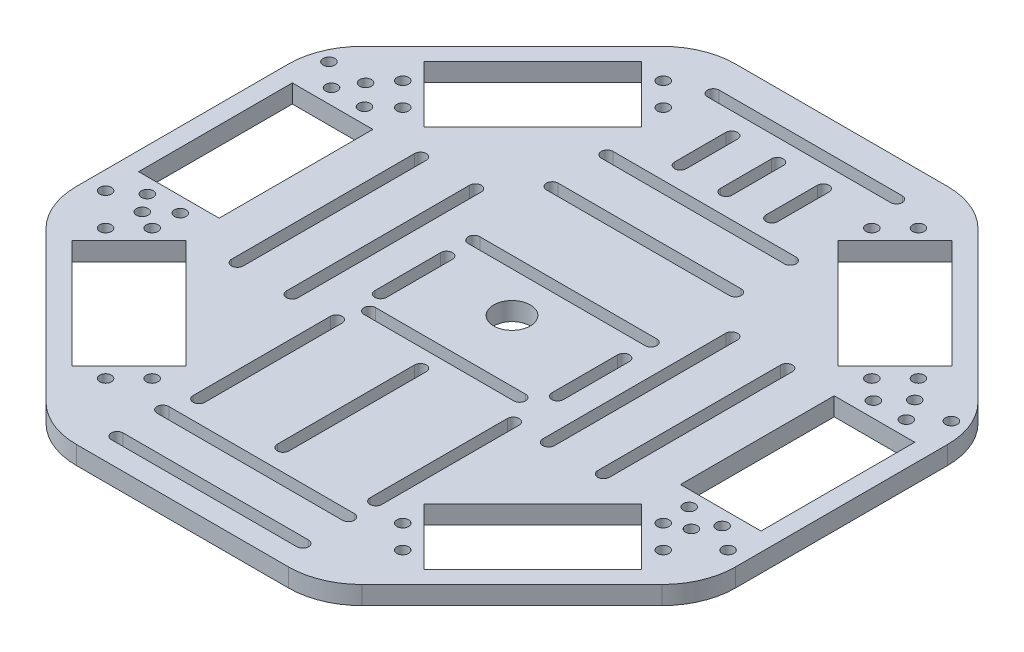
SolidWorks part; units mm, degrees
ref_plane "Front Plane" through (0, 0, 0) normal (0, 0, 1) x (1, 0, 0)
ref_plane "Top Plane" through (0, 0, 0) normal (0, 1, 0) x (1, 0, 0)
ref_plane "Right Plane" through (0, 0, 0) normal (1, 0, 0) x (0, 0, -1)
sketch "Sketch1" plane through (0, 0, 0) normal (0, 1, 0) x (1, 0, 0)
  line L1 (-90, -37.2792) -> (-37.2792, -90)
  line L2 (-37.2792, -90) -> (37.2792, -90)
  line L3 (37.2792, -90) -> (90, -37.2792)
  line L4 (90, -37.2792) -> (90, 37.2792)
  line L5 (90, 37.2792) -> (37.2792, 90)
  line L6 (37.2792, 90) -> (-37.2792, 90)
  line L7 (-37.2792, 90) -> (-90, 37.2792)
  line L8 (-90, 37.2792) -> (-90, -37.2792)
  line L12 (63.6396, -63.6396) -> (0, 0) construction
  line L21 (-20.4, -34.5422) -> (-34.5422, -20.4)
  line L22 (-20.4, -34.5422) -> (-50.0985, -64.2407)
  line L23 (-50.0985, -64.2407) -> (-64.2407, -50.0985)
  line L24 (-34.5422, -20.4) -> (-64.2407, -50.0985)
  line L25 (-38.85, -10) -> (-38.85, 10)
  line L26 (-38.85, -10) -> (-80.85, -10)
  line L27 (-80.85, -10) -> (-80.85, 10)
  line L28 (-38.85, 10) -> (-80.85, 10)
  line L29 (-34.5422, 20.4) -> (-20.4, 34.5422)
  line L30 (-34.5422, 20.4) -> (-64.2407, 50.0985)
  line L31 (-64.2407, 50.0985) -> (-50.0985, 64.2407)
  line L32 (-20.4, 34.5422) -> (-50.0985, 64.2407)
  line L37 (20.4, 34.5422) -> (34.5422, 20.4)
  line L38 (20.4, 34.5422) -> (50.0985, 64.2407)
  line L39 (50.0985, 64.2407) -> (64.2407, 50.0985)
  line L40 (34.5422, 20.4) -> (64.2407, 50.0985)
  line L41 (38.85, 10) -> (38.85, -10)
  line L42 (38.85, 10) -> (80.85, 10)
  line L43 (80.85, 10) -> (80.85, -10)
  line L44 (38.85, -10) -> (80.85, -10)
  circle A0 centre (0, 0) radius 90 construction
  circle A13 centre (0, 0) radius 90 construction
  circle A14 centre (-27.7186, -21.3546) radius 2.5
  circle A15 centre (-21.3546, -27.7186) radius 2.5
  circle A16 centre (-56.9221, -63.2861) radius 2.5
  circle A17 centre (-63.2861, -56.9221) radius 2.5
  circle A18 centre (0, 0) radius 90 construction
  circle A19 centre (-34.7, 4.5) radius 2.5
  circle A20 centre (-34.7, -4.5) radius 2.5
  circle A21 centre (-85, -4.5) radius 2.5
  circle A22 centre (-85, 4.5) radius 2.5
  circle A23 centre (0, 0) radius 90 construction
  circle A24 centre (-21.3546, 27.7186) radius 2.5
  circle A25 centre (-27.7186, 21.3546) radius 2.5
  circle A26 centre (-63.2861, 56.9221) radius 2.5
  circle A27 centre (-56.9221, 63.2861) radius 2.5
  circle A28 centre (0, 0) radius 90 construction
  circle A33 centre (0, 0) radius 90 construction
  circle A34 centre (27.7186, 21.3546) radius 2.5
  circle A35 centre (21.3546, 27.7186) radius 2.5
  circle A36 centre (56.9221, 63.2861) radius 2.5
  circle A37 centre (63.2861, 56.9221) radius 2.5
  circle A38 centre (0, 0) radius 90 construction
  circle A39 centre (34.7, -4.5) radius 2.5
  circle A40 centre (34.7, 4.5) radius 2.5
  circle A41 centre (85, 4.5) radius 2.5
  circle A42 centre (85, -4.5) radius 2.5
  circle A43 centre (0, 0) radius 90 construction
  point P15 (63.6396, -63.6396)
  point P16 (60.1041, -60.1041)
  point P17 (57.1696, -57.1696)
  point P121 (0, 0)
  dimension "D1" = 90
  dimension "D12" = 8
extrude "Baseplate" add sketch "Sketch1" along normal blind 5 contours L7 L8 L1 L2 L3 L4 L5 L6 A42 A41 A40 A39 A37 A36 A35 A34 A27 A26 A25 A24 A22 A21 A20 A19 A17 A16 A15 A14 L44 L41 | L29 L32 L31 L30 | L37 L40 L39 L38 | L41 L44 L43 L42 | L25 L28 L27 L26 | A27 | A26 | A25 | A24 | A22 | A21 | A19 | A20 | A14 | A15 | A17 | A16 | A40 | A41 | A42 | A35 | A34 | A39 | A37 | A36 | L21 L24 L23 L22 region at (1.7472, 0, 1.7472) region at (-59.85, 0, 0) region at (-42.3203, 0, -42.3203) region at (42.3203, 0, -42.3203) region at (59.85, 0, 0) region at (-27.7186, 0, 21.3546) region at (-21.3546, 0, 27.7186) region at (-56.9221, 0, 63.2861) region at (-63.2861, 0, 56.9221) region at (-34.7, 0, -4.5) region at (-34.7, 0, 4.5) region at (-85, 0, 4.5) region at (-85, 0, -4.5) region at (-21.3546, 0, -27.7186) region at (-27.7186, 0, -21.3546) region at (-63.2861, 0, -56.9221) region at (-56.9221, 0, -63.2861) region at (34.7, 0, -4.5) region at (85, 0, -4.5) region at (85, 0, 4.5)
fillet "Fillet1" radius 20 8 edges at (-90, 2.5, -37.2792) (-37.2792, 2.5, -90) (37.2792, 2.5, -90) (90, 2.5, -37.2792) (90, 2.5, 37.2792) (37.2792, 2.5, 90) (-37.2792, 2.5, 90) (-90, 2.5, 37.2792)
sketch "Sketch2" plane through (0, 5, 0) normal (0, 1, 0) x (1, 0, 0)
  line L0 (90, -28.9949) -> (90, 28.9949) construction
  line L1 (63, 25.0051) -> (85, 25.0051)
  line L2 (63, 25.0051) -> (63, -16.9949)
  line L3 (63, -16.9949) -> (85, -16.9949)
  line L4 (85, 25.0051) -> (85, -16.9949)
  circle A0 centre (78.5, 29.2051) radius 1.6
  circle A1 centre (69.5, 29.2051) radius 1.6
  circle A2 centre (69.5, -21.0949) radius 1.6
  circle A3 centre (78.5, -21.0949) radius 1.6
  point P8 (74, 25.0051)
  dimension "D1" = 3.2
  dimension "D2" = 9
  dimension "D3" = 50.3
  dimension "D4" = 22
  dimension "D5" = 42
  dimension "D6" = 4.2
  dimension "D7" = 4.5
  dimension "D8" = 5
  dimension "D9" = 12
extrude "Servo hole" cut sketch "Sketch2" against normal through all contours A0 | L4 L1 L2 L3 | A2 | A3 | A1 region at (74, 5, -4.0051) region at (78.5, 5, -29.2051) region at (69.5, 5, 21.0949) region at (78.5, 5, 21.0949)
sketch "Sketch3" plane through (0, 5, 0) normal (0, 1, 0) x (1, 0, 0)
  circle A0 centre (0, 0) radius 5
  dimension "D1" = 10
extrude "Center hole" cut sketch "Sketch3" against normal through all
pattern_circular "Servo hole pattern" count 8 over 360 about axis through (0, 5, 0) along (0, 1, 0) skipping 2, 3, 4, 5, 6 of "Servo hole"
sketch "Sketch4" plane through (0, 5, 0) normal (0, 1, 0) x (1, 0, 0)
  line L0 (-28.9949, -90) -> (28.9949, -90) construction
  line L1 (-90, 28.9949) -> (-90, -28.9949) construction
  circle A0 centre (-23, 5.1332) radius 1.6
  circle A1 centre (-23, -70) radius 1.6
  circle A2 centre (25.3362, 12.6262) radius 1.6
  circle A3 centre (25.3362, -70) radius 1.6
  circle A4 centre (-7.5585, -18.3745) radius 1.6
  circle A5 centre (20.4577, -18.3745) radius 1.6
  dimension "D1" = 3.2
  dimension "D8" = 20
  dimension "D2" = 7.493
  dimension "D3" = 48.3362
  dimension "D4" = 31.0007
  dimension "D5" = 51.6255
  dimension "D6" = 4.8785
  dimension "D7" = 28.0162
  dimension "D9" = 67
extrude "Arduino Screw holes" cut sketch "Sketch4" against normal through all
ref_plane "Midplane" through (0, 0, 0) normal (1, 0, 0) x (0, 0, -1)
mirror "Mirror1" about plane through (0, 0, 0) normal (1, 0, 0) of "Servo hole pattern", "Servo hole"
sketch "Sketch5" plane through (0, 5, 0) normal (0, 1, 0) x (1, 0, 0)
  line L0 (-25, 36) -> (25, 36) construction
  line L1 (-25, 37.6) -> (25, 37.6)
  line L2 (-25, 34.4) -> (25, 34.4)
  line L3 (-25, 51) -> (25, 51) construction
  line L4 (-25, 52.6) -> (25, 52.6)
  line L5 (-25, 49.4) -> (25, 49.4)
  line L6 (-50, 25) -> (-50, -25) construction
  line L7 (-48.4, 25) -> (-48.4, -25)
  line L8 (-51.6, 25) -> (-51.6, -25)
  line L9 (-35, 25) -> (-35, -25) construction
  line L10 (-33.4, 25) -> (-33.4, -25)
  line L11 (-36.6, 25) -> (-36.6, -25)
  line L12 (35, 25) -> (35, -25) construction
  line L13 (36.6, 25) -> (36.6, -25)
  line L14 (33.4, 25) -> (33.4, -25)
  line L15 (50, 25) -> (50, -25) construction
  line L16 (51.6, 25) -> (51.6, -25)
  line L17 (48.4, 25) -> (48.4, -25)
  line L18 (-25, 80) -> (25, 80) construction
  line L19 (-25, 81.6) -> (25, 81.6)
  line L20 (-25, 78.4) -> (25, 78.4)
  line L21 (-12.5, 72.5) -> (-12.5, 58.5) construction
  line L22 (-10.9, 72.5) -> (-10.9, 58.5)
  line L23 (-14.1, 72.5) -> (-14.1, 58.5)
  line L24 (12.5, 72.5) -> (12.5, 58.5) construction
  line L25 (14.1, 72.5) -> (14.1, 58.5)
  line L26 (10.9, 72.5) -> (10.9, 58.5)
  line L27 (28.9949, 90) -> (-28.9949, 90) construction
  line L28 (0, 72.5) -> (0, 58.5) construction
  line L29 (1.6, 72.5) -> (1.6, 58.5)
  line L30 (-1.6, 72.5) -> (-1.6, 58.5)
  arc A0 (-25, 37.6) -> (-25, 34.4) centre (-25, 36) ccw
  arc A1 (25, 34.4) -> (25, 37.6) centre (25, 36) ccw
  arc A2 (-25, 52.6) -> (-25, 49.4) centre (-25, 51) ccw
  arc A3 (25, 49.4) -> (25, 52.6) centre (25, 51) ccw
  arc A4 (-48.4, 25) -> (-51.6, 25) centre (-50, 25) ccw
  arc A5 (-51.6, -25) -> (-48.4, -25) centre (-50, -25) ccw
  arc A6 (-33.4, 25) -> (-36.6, 25) centre (-35, 25) ccw
  arc A7 (-36.6, -25) -> (-33.4, -25) centre (-35, -25) ccw
  arc A8 (36.6, 25) -> (33.4, 25) centre (35, 25) ccw
  arc A9 (33.4, -25) -> (36.6, -25) centre (35, -25) ccw
  arc A10 (51.6, 25) -> (48.4, 25) centre (50, 25) ccw
  arc A11 (48.4, -25) -> (51.6, -25) centre (50, -25) ccw
  arc A12 (-25, 81.6) -> (-25, 78.4) centre (-25, 80) ccw
  arc A13 (25, 78.4) -> (25, 81.6) centre (25, 80) ccw
  arc A14 (-10.9, 72.5) -> (-14.1, 72.5) centre (-12.5, 72.5) ccw
  arc A15 (-14.1, 58.5) -> (-10.9, 58.5) centre (-12.5, 58.5) ccw
  arc A16 (14.1, 72.5) -> (10.9, 72.5) centre (12.5, 72.5) ccw
  arc A17 (10.9, 58.5) -> (14.1, 58.5) centre (12.5, 58.5) ccw
  arc A18 (1.6, 72.5) -> (-1.6, 72.5) centre (0, 72.5) ccw
  arc A19 (-1.6, 58.5) -> (1.6, 58.5) centre (0, 58.5) ccw
  point P2 (0, 36)
  point P7 (0, 51)
  point P14 (-50, 0)
  point P21 (-35, 0)
  point P28 (35, 0)
  point P35 (50, 0)
  point P42 (0, 80)
  point P48 (-12.5, 65.5)
  point P57 (12.5, 65.5)
  point P64 (0, 65.5)
  dimension "D1" = 1.6
  dimension "D7" = 50
  dimension "D2" = 15
  dimension "D3" = 15
  dimension "D4" = 15
  dimension "D5" = 10
  dimension "D6" = 50
  dimension "D8" = 35
  dimension "D9" = 35
  dimension "D10" = 36
  dimension "D11" = 12.5
  dimension "D12" = 12.5
  dimension "D13" = 7.5
  dimension "D14" = 7.5
extrude "Slits" cut sketch "Sketch5" against normal through all contours L30 A19 L29 A18 | L26 A17 L25 A16 | L5 A3 L4 A2 | L2 A1 L1 A0 | L8 A5 L7 A4 | L11 A7 L10 A6 | L14 A9 L13 A8 | L17 A11 L16 A10 | L19 A13 L20 A12 | L22 A15 L23 A14 region at (0, 5, -36) region at (0, 5, -51) region at (-50, 5, 0) region at (-35, 5, 0) region at (35, 5, 0) region at (50, 5, 0) region at (12.5, 5, -65.5) region at (0, 5, -65.5)
sketch "Sketch6" plane through (0, 5, 0) normal (0, 1, 0) x (1, 0, 0)
  circle A0 centre (-75, 35) radius 1.6
  circle A1 centre (-85, 35) radius 1.6
  point P4 (0, 0)
  dimension "D1" = 3.2
  dimension "D3" = 10
  dimension "D4" = 85
  dimension "D5" = 35
extrude "Exterior Screw Holes" cut sketch "Sketch6" against normal through all
ref_plane "Plane1" through (0, 0, 0) normal (0, 0, 1) x (1, 0, 0)
mirror "Mirror2" about plane through (0, 0, 0) normal (1, 0, 0) of "Exterior Screw Holes"
sketch "Sketch7" plane through (0, 5, 0) normal (0, 1, 0) x (1, 0, 0)
  line L0 (-85, 35) -> (-85, 2.3324)
  circle A0 centre (-85, -26) radius 1.6
  circle A1 centre (-75, -26) radius 1.6
  point P4 (-86.5, -19.8866)
  point P5 (0, 0)
  dimension "D1" = 3.2
  dimension "D3" = 10
  dimension "D4" = 61
extrude "Cut-Extrude1" cut sketch "Sketch7" against normal through all contours A1 | A0 region at (-75, 5, 26)
mirror "Mirror3" about plane through (0, 0, 0) normal (1, 0, 0) of "Cut-Extrude1"
sketch "Sketch8" plane through (0, 5, 0) normal (0, 1, 0) x (1, 0, 0)
  line L0 (20.4577, -18.3745) -> (-20.4577, -18.3745) construction
  line L1 (20.4577, -19.9745) -> (-20.4577, -19.9745)
  line L2 (20.4577, -16.7745) -> (-20.4577, -16.7745)
  line L3 (0, -25.4762) -> (0, 25.4762) construction
  line L4 (25.3362, 12.6262) -> (-23, 12.6262) construction
  line L5 (25.3362, 11.0262) -> (-23, 11.0262)
  line L6 (25.3362, 14.2262) -> (-23, 14.2262)
  line L7 (-23, -12.8668) -> (-23, 5.1332) construction
  line L8 (-24.6, -12.8668) -> (-24.6, 5.1332)
  line L9 (-21.4, -12.8668) -> (-21.4, 5.1332)
  line L10 (25.3362, 5.1332) -> (25.3362, -12.8668) construction
  line L11 (26.9362, 5.1332) -> (26.9362, -12.8668)
  line L12 (23.7362, 5.1332) -> (23.7362, -12.8668)
  line L13 (-25.3362, -70) -> (25.3362, -70) construction
  line L14 (-25.3362, -68.4) -> (25.3362, -68.4)
  line L15 (-25.3362, -71.6) -> (25.3362, -71.6)
  line L16 (-23, -25) -> (-23, -62.5) construction
  line L17 (-21.4, -25) -> (-21.4, -62.5)
  line L18 (-24.6, -25) -> (-24.6, -62.5)
  line L19 (25.3362, -62.5) -> (25.3362, -25) construction
  line L20 (23.7362, -62.5) -> (23.7362, -25)
  line L21 (26.9362, -62.5) -> (26.9362, -25)
  line L22 (0, -62.5) -> (0, -25) construction
  line L23 (-1.6, -62.5) -> (-1.6, -25)
  line L24 (1.6, -62.5) -> (1.6, -25)
  line L25 (-25.3362, -82.5) -> (25.3362, -82.5) construction
  line L26 (-25.3362, -80.9) -> (25.3362, -80.9)
  line L27 (-25.3362, -84.1) -> (25.3362, -84.1)
  arc A0 (20.4577, -19.9745) -> (20.4577, -16.7745) centre (20.4577, -18.3745) ccw
  arc A1 (-20.4577, -16.7745) -> (-20.4577, -19.9745) centre (-20.4577, -18.3745) ccw
  circle A2 centre (-7.5585, -18.3745) radius 1.6 construction
  arc A3 (25.3362, 11.0262) -> (25.3362, 14.2262) centre (25.3362, 12.6262) ccw
  arc A4 (-23, 14.2262) -> (-23, 11.0262) centre (-23, 12.6262) ccw
  arc A5 (-24.6, -12.8668) -> (-21.4, -12.8668) centre (-23, -12.8668) ccw
  arc A6 (-21.4, 5.1332) -> (-24.6, 5.1332) centre (-23, 5.1332) ccw
  arc A7 (26.9362, 5.1332) -> (23.7362, 5.1332) centre (25.3362, 5.1332) ccw
  arc A8 (23.7362, -12.8668) -> (26.9362, -12.8668) centre (25.3362, -12.8668) ccw
  arc A9 (-25.3362, -68.4) -> (-25.3362, -71.6) centre (-25.3362, -70) ccw
  arc A10 (25.3362, -71.6) -> (25.3362, -68.4) centre (25.3362, -70) ccw
  arc A11 (-21.4, -25) -> (-24.6, -25) centre (-23, -25) ccw
  arc A12 (-24.6, -62.5) -> (-21.4, -62.5) centre (-23, -62.5) ccw
  arc A13 (23.7362, -62.5) -> (26.9362, -62.5) centre (25.3362, -62.5) ccw
  arc A14 (26.9362, -25) -> (23.7362, -25) centre (25.3362, -25) ccw
  arc A15 (-1.6, -62.5) -> (1.6, -62.5) centre (0, -62.5) ccw
  arc A16 (1.6, -25) -> (-1.6, -25) centre (0, -25) ccw
  arc A17 (-25.3362, -80.9) -> (-25.3362, -84.1) centre (-25.3362, -82.5) ccw
  arc A18 (25.3362, -84.1) -> (25.3362, -80.9) centre (25.3362, -82.5) ccw
  point P3 (0, -18.3745)
  point P8 (1.1681, 12.6262)
  point P20 (-23, -3.8668)
  point P30 (25.3362, -3.8668)
  point P35 (0, -70)
  point P40 (-23, -43.75)
  point P50 (25.3362, -43.75)
  point P57 (0, -43.75)
  point P65 (0, -82.5)
  dimension "D2" = 1.6
  dimension "D1" = 18
  dimension "D3" = 37.5
  dimension "D4" = 7.5
  dimension "D5" = 12.5
extrude "Cut-Extrude2" cut sketch "Sketch8" against normal through all contours L9 A6 L8 A5 | L12 A8 L11 A7 | L2 A1 L1 A0 | L24 A16 L23 A15 | L21 A14 L20 A13 | L27 A18 L26 A17 | L6 A4 L5 A3 | L17 A12 L18 A11 | L14 A10 L15 A9 region at (0, 5, 18.3745) region at (-23, 5, 3.8668) region at (25.3362, 5, 3.8668) region at (25.3362, 5, 43.75) region at (0, 5, 43.75) region at (0, 5, 82.5)
